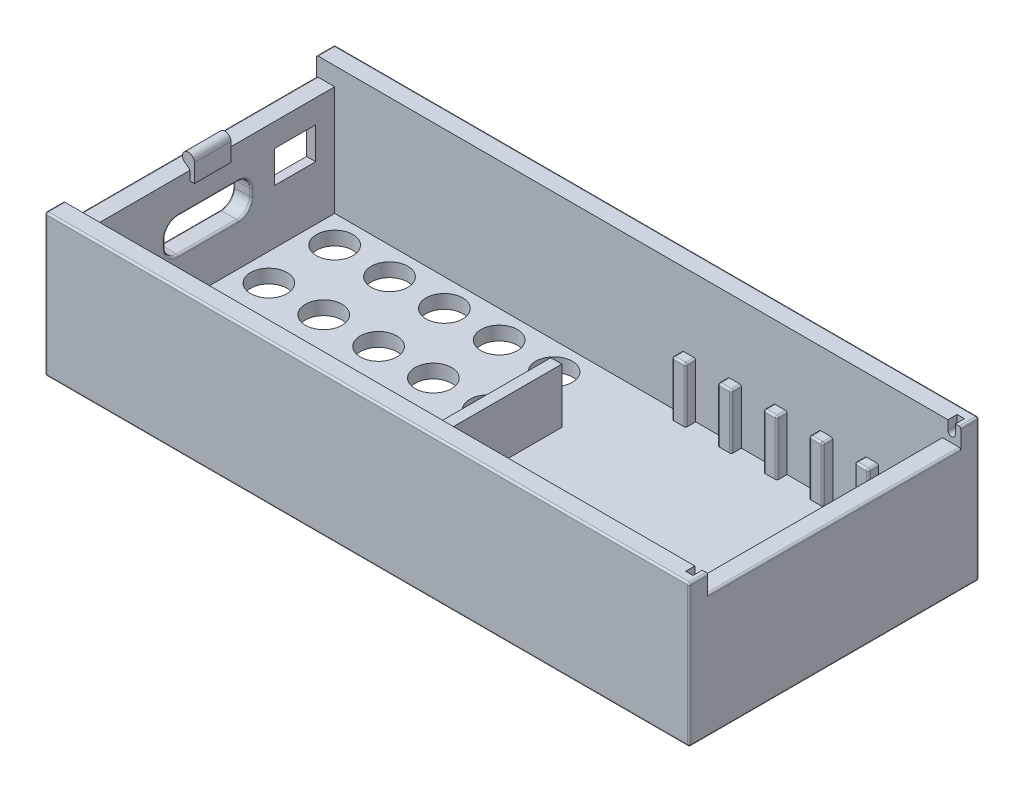
SolidWorks part; units mm, degrees
material "PLA"
ref_plane "前视基准面" through (0, 0, 0) normal (0, 0, 1) x (1, 0, 0)
ref_plane "上视基准面" through (0, 0, 0) normal (0, 1, 0) x (1, 0, 0)
ref_plane "右视基准面" through (0, 0, 0) normal (1, 0, 0) x (0, 0, -1)
sketch "草图1" plane through (0, 0, 0) normal (0, 0, 1) x (1, 0, 0)
  line L0 (0, 0) -> (70.5, 0)
  line L1 (70.5, 0) -> (70.5, 13.5)
  line L2 (70.5, 13.5) -> (68.5, 13.5)
  line L3 (68.5, 13.5) -> (68.5, 1.5)
  line L4 (68.5, 1.5) -> (2, 1.5)
  line L5 (2, 1.5) -> (2, 13.5)
  line L6 (2, 13.5) -> (0, 13.5)
  line L7 (0, 13.5) -> (0, 0)
  dimension "D1" = 66.5
  dimension "D3" = 2
  dimension "D4" = 1.5
  dimension "D6" = 12
extrude "凸台-拉伸1" add sketch "草图1" along normal blind 31.7
sketch "草图3" plane through (0, 1.5, 0) normal (0, 1, 0) x (1, 0, 0)
  line L0 (2, -31.7) -> (68.5, -31.7)
  line L1 (68.5, -31.7) -> (68.5, -29.7)
  line L2 (68.5, -31.7) -> (68.5, 0) construction
  line L3 (68.5, -29.7) -> (2, -29.7)
  line L4 (2, -31.7) -> (2, 0) construction
  line L5 (2, -29.7) -> (2, -31.7)
  dimension "D1" = 2
extrude "凸台-拉伸2" add sketch "草图3" along normal through all
sketch "草图4" plane through (0, 1.5, 0) normal (0, 1, 0) x (1, 0, 0)
  line L0 (2, 0) -> (68.5, 0)
  line L1 (68.5, -29.7) -> (68.5, 0) construction
  line L2 (68.5, -29.7) -> (68.5, 0) construction
  line L3 (68.5, 0) -> (68.5, -2)
  line L4 (68.5, -2) -> (2, -2)
  line L5 (2, -29.7) -> (2, 0) construction
  line L6 (2, -2) -> (2, 0)
  dimension "D1" = 2
extrude "凸台-拉伸3" add sketch "草图4" along normal through all
sketch "草图5" plane through (0, 1.5, 0) normal (0, 1, 0) x (1, 0, 0)
  line L0 (34.1, -6.415) -> (34.1, -25.7073) construction
  line L2 (23.9227, -15.85) -> (46.7103, -15.85) construction
  line L3 (2, -2) -> (68.5, -2) construction
  line L4 (68.5, -29.7) -> (2, -29.7) construction
  line L5 (34.7, -9.85) -> (33.5, -9.85)
  line L6 (33.5, -9.85) -> (33.5, -21.85)
  line L7 (34.7, -9.85) -> (34.7, -21.85)
  line L8 (34.7, -21.85) -> (33.5, -21.85)
  line L9 (2, -29.7) -> (2, -2) construction
  point P14 (34.1, -9.85)
  point P16 (34.7, -15.85)
  point P17 (33.5, -15.85)
  dimension "D1" = 1.2
  dimension "D2" = 32.1
  dimension "D3" = 12
extrude "凸台-拉伸4" add sketch "草图5" along normal blind 6 contours L6 L8 L7 L5
sketch "草图10" plane through (0, 0, 0) normal (-1, 0, 0) x (0, 0, 1)
  line L0 (5.075, 9.1862) -> (7.575, 9.1862) construction
  line L1 (5.075, 8.1862) -> (5.075, 10.1862) construction
  line L2 (7.575, 10.1862) -> (7.575, 8.1862) construction
  line L3 (6.325, 8.1862) -> (6.325, 10.1862) construction
  line L4 (7.575, 8.1862) -> (5.075, 8.1862) construction
  line L5 (5.075, 10.1862) -> (7.575, 10.1862) construction
  line L7 (8.575, 7.4362) -> (4.075, 7.4362)
  line L8 (8.575, 7.4362) -> (8.575, 10.9362)
  line L9 (8.575, 10.9362) -> (4.075, 10.9362)
  line L10 (4.075, 7.4362) -> (4.075, 10.9362)
  line L11 (8.575, 7.4362) -> (4.075, 10.9362) construction
  line L12 (8.575, 10.9362) -> (4.075, 7.4362) construction
  point P12 (6.325, 9.1862)
  dimension "D1" = 3.5
  dimension "D2" = 4.5
extrude "切除-拉伸3" cut sketch "草图10" against normal up to next
sketch "草图11" plane through (0, 0, 0) normal (-1, 0, 0) x (0, 0, 1)
  line L14 (11.13, 8.3362) -> (11.13, 7.5762)
  line L15 (12.58, 6.1262) -> (19.12, 6.1262)
  line L16 (20.57, 7.5762) -> (20.57, 8.3362)
  line L17 (19.12, 9.7862) -> (12.58, 9.7862)
  line L18 (11.13, 8.3362) -> (11.13, 7.5762)
  line L19 (12.58, 6.1262) -> (19.12, 6.1262)
  line L20 (20.57, 7.5762) -> (20.57, 8.3362)
  line L21 (19.12, 9.7862) -> (12.58, 9.7862)
  arc A8 (11.13, 7.5762) -> (12.58, 6.1262) centre (12.58, 7.5762) ccw
  arc A9 (19.12, 6.1262) -> (20.57, 7.5762) centre (19.12, 7.5762) ccw
  arc A10 (20.57, 8.3362) -> (19.12, 9.7862) centre (19.12, 8.3362) ccw
  arc A11 (12.58, 9.7862) -> (11.13, 8.3362) centre (12.58, 8.3362) ccw
  arc A12 (11.13, 7.5762) -> (12.58, 6.1262) centre (12.58, 7.5762) ccw
  arc A13 (19.12, 6.1262) -> (20.57, 7.5762) centre (19.12, 7.5762) ccw
  arc A14 (20.57, 8.3362) -> (19.12, 9.7862) centre (19.12, 8.3362) ccw
  arc A15 (12.58, 9.7862) -> (11.13, 8.3362) centre (12.58, 8.3362) ccw
  dimension "D1" = 0.3
extrude "切除-拉伸4" cut sketch "草图11" against normal up to next
sketch "草图14" plane through (0, 0, 2) normal (0, 0, 1) x (1, 0, 0)
  line L0 (66.4954, 1.5) -> (66.4954, 7.5)
  line L1 (2, 1.5) -> (68.5, 1.5) construction
  line L2 (66.4954, 7.5) -> (64.9954, 7.5)
  line L3 (64.9954, 7.5) -> (64.9954, 1.5)
  line L4 (64.9954, 1.5) -> (66.4954, 1.5)
  line L5 (68.5, 13.5) -> (68.5, 1.5) construction
  line L6 (64.1133, 1.5) -> (64.1133, 7.9181) construction
  line L7 (59.9954, 7.5) -> (59.9954, 1.5)
  line L8 (61.4954, 7.5) -> (59.9954, 7.5)
  line L9 (61.4954, 1.5) -> (61.4954, 7.5)
  line L10 (59.9954, 1.5) -> (61.4954, 1.5)
  line L11 (54.9954, 7.5) -> (54.9954, 1.5)
  line L12 (56.4954, 7.5) -> (54.9954, 7.5)
  line L13 (56.4954, 1.5) -> (56.4954, 7.5)
  line L14 (54.9954, 1.5) -> (56.4954, 1.5)
  line L15 (49.9954, 7.5) -> (49.9954, 1.5)
  line L16 (51.4954, 7.5) -> (49.9954, 7.5)
  line L17 (51.4954, 1.5) -> (51.4954, 7.5)
  line L18 (49.9954, 1.5) -> (51.4954, 1.5)
  line L19 (44.9954, 7.5) -> (44.9954, 1.5)
  line L20 (46.4954, 7.5) -> (44.9954, 7.5)
  line L21 (46.4954, 1.5) -> (46.4954, 7.5)
  line L22 (44.9954, 1.5) -> (46.4954, 1.5)
  line L23 (39.9954, 7.5) -> (39.9954, 1.5)
  line L24 (41.4954, 7.5) -> (39.9954, 7.5)
  line L25 (41.4954, 1.5) -> (41.4954, 7.5)
  line L26 (39.9954, 1.5) -> (41.4954, 1.5)
  line L27 (64.9954, 7.5) -> (59.9954, 7.5) construction
  dimension "D1" = 1.5
  dimension "D2" = 6
  dimension "D3" = 2.0046
  dimension "D4" = 0.8821
  dimension "D6" = 5
  dimension "D5" = 6
extrude "凸台-拉伸7" add sketch "草图14" along normal blind 1.1
fillet "圆角5" radius 0.2 18 edges at (66.4954, 4.5, 3.1) (65.7454, 7.5, 3.1) (64.9954, 4.5, 3.1) (61.4954, 4.5, 3.1) (60.7454, 7.5, 3.1) (59.9954, 4.5, 3.1) (56.4954, 4.5, 3.1) (55.7454, 7.5, 3.1) (54.9954, 4.5, 3.1) (51.4954, 4.5, 3.1) (50.7454, 7.5, 3.1) (49.9954, 4.5, 3.1) (46.4954, 4.5, 3.1) (45.7454, 7.5, 3.1) (44.9954, 4.5, 3.1) (41.4954, 4.5, 3.1) (40.7454, 7.5, 3.1) (39.9954, 4.5, 3.1)
fillet "圆角6" radius 0.2 24 edges at (66.4368, 7.4414, 3.0414) (65.0539, 7.4414, 3.0414) (60.0539, 7.4414, 3.0414) (61.4368, 7.4414, 3.0414) (56.4368, 7.4414, 3.0414) (51.4368, 7.4414, 3.0414) (46.4368, 7.4414, 3.0414) (41.4368, 7.4414, 3.0414) (55.0539, 7.4414, 3.0414) (50.0539, 7.4414, 3.0414) (45.0539, 7.4414, 3.0414) (40.0539, 7.4414, 3.0414) (66.4954, 7.5, 2.45) (64.9954, 7.5, 2.45) (59.9954, 7.5, 2.45) (61.4954, 7.5, 2.45) (56.4954, 7.5, 2.45) (51.4954, 7.5, 2.45) (46.4954, 7.5, 2.45) (41.4954, 7.5, 2.45) (54.9954, 7.5, 2.45) (49.9954, 7.5, 2.45) (44.9954, 7.5, 2.45) (39.9954, 7.5, 2.45)
sketch "草图15" plane through (0, 0, 29.7) normal (0, 0, -1) x (-1, 0, 0)
  line L0 (-68.5, 1.5) -> (-2, 1.5) construction
  line L1 (-66.5, 1.5) -> (-65, 1.5)
  line L2 (-66.5, 1.5) -> (-66.5, 7.5)
  line L3 (-66.5, 7.5) -> (-65, 7.5)
  line L4 (-65, 1.5) -> (-65, 7.5)
  line L5 (-68.5, 13.5) -> (-68.5, 1.5) construction
  line L6 (-61.5, 1.5) -> (-61.5, 7.5)
  line L7 (-61.5, 7.5) -> (-60, 7.5)
  line L8 (-60, 1.5) -> (-60, 7.5)
  line L9 (-61.5, 1.5) -> (-60, 1.5)
  line L10 (-56.5, 1.5) -> (-56.5, 7.5)
  line L11 (-56.5, 7.5) -> (-55, 7.5)
  line L12 (-55, 1.5) -> (-55, 7.5)
  line L13 (-56.5, 1.5) -> (-55, 1.5)
  line L14 (-51.5, 1.5) -> (-51.5, 7.5)
  line L15 (-51.5, 7.5) -> (-50, 7.5)
  line L16 (-50, 1.5) -> (-50, 7.5)
  line L17 (-51.5, 1.5) -> (-50, 1.5)
  line L18 (-46.5, 1.5) -> (-46.5, 7.5)
  line L19 (-46.5, 7.5) -> (-45, 7.5)
  line L20 (-45, 1.5) -> (-45, 7.5)
  line L21 (-46.5, 1.5) -> (-45, 1.5)
  line L22 (-41.5, 1.5) -> (-41.5, 7.5)
  line L23 (-41.5, 7.5) -> (-40, 7.5)
  line L24 (-40, 1.5) -> (-40, 7.5)
  line L25 (-41.5, 1.5) -> (-40, 1.5)
  line L26 (-66.5, 1.5) -> (-61.5, 1.5) construction
  dimension "D1" = 2
  dimension "D2" = 1.5
  dimension "D3" = 6
  dimension "D5" = 5
  dimension "D4" = 6
extrude "凸台-拉伸8" add sketch "草图15" along normal blind 1.1
fillet "圆角7" radius 0.2 30 edges at (40, 7.5, 29.15) (40.75, 7.5, 28.6) (40, 4.5, 28.6) (41.5, 4.5, 28.6) (41.5, 7.5, 29.15) (45, 4.5, 28.6) (46.5, 4.5, 28.6) (45, 7.5, 29.15) (45.75, 7.5, 28.6) (46.5, 7.5, 29.15) (50, 7.5, 29.15) (50, 4.5, 28.6) (50.75, 7.5, 28.6) (51.5, 4.5, 28.6) (51.5, 7.5, 29.15) (55, 7.5, 29.15) (55.75, 7.5, 28.6) (55, 4.5, 28.6) (56.5, 4.5, 28.6) (56.5, 7.5, 29.15) (61.5, 7.5, 29.15) (60, 7.5, 29.15) (60.75, 7.5, 28.6) (60, 4.5, 28.6) (61.5, 4.5, 28.6) (66.5, 4.5, 28.6) (65, 4.5, 28.6) (65, 7.5, 29.15) (65.75, 7.5, 28.6) (66.5, 7.5, 29.15)
sketch "草图16" plane through (0, 0, 0) normal (-1, 0, 0) x (0, 0, 1)
  line L0 (0, 13.5) -> (0, 15.5)
  line L1 (0, 15.5) -> (2, 15.5)
  line L2 (2, 15.5) -> (2, 13.5)
  line L3 (31.7, 13.5) -> (0, 13.5) construction
  line L4 (2, 13.5) -> (0, 13.5)
  line L5 (15.85, 0) -> (15.85, 20.1555) construction
  line L6 (31.7, 0) -> (0, 0) construction
  line L7 (29.7, 13.5) -> (31.7, 13.5)
  line L8 (29.7, 15.5) -> (29.7, 13.5)
  line L9 (31.7, 15.5) -> (29.7, 15.5)
  line L10 (31.7, 13.5) -> (31.7, 15.5)
  dimension "D1" = 2
  dimension "D2" = 2
extrude "凸台-拉伸9" add sketch "草图16" against normal through all
fillet "圆角8" radius 0.2 8 edges at (0, 6.5509, 20.1453) (0, 6.1262, 15.85) (0, 6.5509, 11.5547) (0, 7.9562, 11.13) (0, 9.3615, 11.5547) (0, 9.7862, 15.85) (0, 9.3615, 20.1453) (0, 7.9562, 20.57)
fillet "圆角9" radius 0.2 4 edges at (70.5, 13.5, 15.85) (0, 13.5, 15.85) (35.25, 15.5, 0) (35.25, 15.5, 31.7)
fillet "圆角10" radius 0.2 16 edges at (70.5, 15.5, 1.1) (70.5, 15.4414, 0.0586) (70.5, 15.5, 30.6) (70.5, 15.4414, 31.6414) (0, 15.5, 30.6) (0, 15.4414, 31.6414) (0, 15.5, 1.1) (0, 15.4414, 0.0586) (35.25, 0, 0) (70.5, 0, 15.85) (70.5, 7.65, 0) (70.5, 7.65, 31.7) (35.25, 0, 31.7) (0, 7.65, 31.7) (0, 0, 15.85) (0, 7.65, 0)
fillet "圆角11" radius 0.2 8 edges at (2, 6.5509, 20.1453) (2, 7.9562, 20.57) (2, 9.3615, 20.1453) (2, 9.7862, 15.85) (2, 9.3615, 11.5547) (2, 7.9562, 11.13) (2, 6.5509, 11.5547) (2, 6.1262, 15.85)
sketch "草图17" plane through (0, 0, 0) normal (-1, 0, 0) x (0, 0, 1)
  line L8 (9.575, 6.4362) -> (9.575, 11.9362)
  line L9 (3.075, 6.4362) -> (9.575, 6.4362)
  line L10 (3.075, 11.9362) -> (3.075, 6.4362)
  line L11 (9.575, 11.9362) -> (3.075, 11.9362)
  line L12 (9.575, 6.4362) -> (9.575, 11.9362)
  line L13 (3.075, 6.4362) -> (9.575, 6.4362)
  line L14 (3.075, 11.9362) -> (3.075, 6.4362)
  line L15 (9.575, 11.9362) -> (3.075, 11.9362)
  dimension "D1" = 1
extrude "切除-拉伸5" cut sketch "草图17" against normal blind 1
chamfer "倒角1" distance 0.5 angle 45 4 edges at (0, 9.1862, 9.575) (0, 11.9362, 6.325) (0, 9.1862, 3.075) (0, 6.4362, 6.325)
sketch "草图18" plane through (0, 1.5, 0) normal (0, 1, 0) x (1, 0, 0)
  line L0 (5, -5) -> (11, -5) construction
  line L1 (5, -5) -> (5, -12.2) construction
  line L2 (5, -5) -> (11, -5) construction
  circle A0 centre (5, -5) radius 2
  circle A1 centre (11, -5) radius 2
  circle A2 centre (17, -5) radius 2
  circle A3 centre (23, -5) radius 2
  circle A4 centre (29, -5) radius 2
  circle A5 centre (5, -12.2) radius 2
  circle A6 centre (5, -19.4) radius 2
  circle A7 centre (5, -26.6) radius 2
  circle A8 centre (11, -5) radius 2
  circle A9 centre (11, -12.2) radius 2
  circle A10 centre (11, -19.4) radius 2
  circle A11 centre (11, -26.6) radius 2
  circle A12 centre (17, -5) radius 2
  circle A13 centre (17, -12.2) radius 2
  circle A14 centre (17, -19.4) radius 2
  circle A15 centre (17, -26.6) radius 2
  circle A16 centre (23, -5) radius 2
  circle A17 centre (23, -12.2) radius 2
  circle A18 centre (23, -19.4) radius 2
  circle A19 centre (23, -26.6) radius 2
  circle A20 centre (29, -5) radius 2
  circle A21 centre (29, -12.2) radius 2
  circle A22 centre (29, -19.4) radius 2
  circle A23 centre (29, -26.6) radius 2
  dimension "D1" = 5
  dimension "D2" = 5
  dimension "D3" = 4
  dimension "D5" = 6
  dimension "D7" = 7.2
  dimension "D9" = 6
  dimension "D4" = 5
  dimension "D6" = 4
  dimension "D8" = 5
extrude "切除-拉伸6" cut sketch "草图18" against normal through all contours A11 | A10 | A7 | A6 | A14 | A18 | A22 | A15 | A19 | A23 | A21 | A17 | A13 | A9 | A5 | A0 | A1 | A2 | A3 | A4 region at (5, 1.5, 5) region at (11, 1.5, 5) region at (17, 1.5, 5) region at (23, 1.5, 5) region at (29, 1.5, 5) region at (5, 1.5, 12.2) region at (5, 1.5, 19.4) region at (5, 1.5, 26.6) region at (11, 1.5, 12.2) region at (11, 1.5, 19.4) region at (11, 1.5, 26.6) region at (17, 1.5, 12.2) region at (17, 1.5, 19.4) region at (17, 1.5, 26.6) region at (23, 1.5, 12.2) region at (23, 1.5, 19.4) region at (23, 1.5, 26.6) region at (29, 1.5, 12.2) region at (29, 1.5, 19.4) region at (29, 1.5, 26.6)
sketch "草图19" plane through (0, 0, 2) normal (0, 0, 1) x (1, 0, 0)
  line L0 (68.5, 13.5) -> (70.5, 13.5) construction
  line L1 (70.5, 13.3) -> (70.5, 15.3) construction
  line L2 (69.5, 13.5) -> (69.5, 15.5) construction
  line L3 (70.3, 15.5) -> (0.2, 15.5) construction
  line L4 (69.9, 14.5) -> (69.9, 15.5)
  line L5 (69.1, 14.5) -> (69.1, 15.5)
  line L6 (69.1, 15.5) -> (69.9, 15.5)
  arc A0 (69.1, 14.5) -> (69.9, 14.5) centre (69.5, 14.5) ccw
  dimension "D1" = 0.8
extrude "切除-拉伸7" cut sketch "草图19" against normal blind 1
sketch "草图20" plane through (0, 0, 29.7) normal (0, 0, -1) x (-1, 0, 0)
  line L0 (-69.9, 14.5) -> (-69.9, 15.5) construction
  line L1 (-69.1, 15.5) -> (-69.1, 14.5) construction
  line L2 (-69.9, 14.5) -> (-69.9, 15.5)
  line L3 (-69.1, 15.5) -> (-69.1, 14.5)
  line L4 (-69.9, 15.5) -> (-69.1, 15.5)
  line L32 (-0.2, 15.5) -> (-70.3, 15.5)
  line L33 (-70.5, 15.3) -> (-70.5, 13.3)
  line L34 (-70.3, 13.5) -> (-68.5, 13.5)
  line L35 (-68.5, 13.5) -> (-68.5, 1.5)
  line L36 (-68.5, 1.5) -> (-66.5, 1.5)
  line L37 (-66.5, 1.5) -> (-66.5, 7.3)
  line L38 (-66.3, 7.5) -> (-65.2, 7.5)
  line L39 (-65, 7.3) -> (-65, 1.5)
  line L40 (-65, 1.5) -> (-61.5, 1.5)
  line L41 (-61.5, 1.5) -> (-61.5, 7.3)
  line L42 (-61.3, 7.5) -> (-60.2, 7.5)
  line L43 (-60, 7.3) -> (-60, 1.5)
  line L44 (-60, 1.5) -> (-56.5, 1.5)
  line L45 (-56.5, 1.5) -> (-56.5, 7.3)
  line L46 (-56.3, 7.5) -> (-55.2, 7.5)
  line L47 (-55, 7.3) -> (-55, 1.5)
  line L48 (-55, 1.5) -> (-51.5, 1.5)
  line L49 (-51.5, 1.5) -> (-51.5, 7.3)
  line L50 (-51.3, 7.5) -> (-50.2, 7.5)
  line L51 (-50, 7.3) -> (-50, 1.5)
  line L52 (-50, 1.5) -> (-46.5, 1.5)
  line L53 (-46.5, 1.5) -> (-46.5, 7.3)
  line L54 (-46.3, 7.5) -> (-45.2, 7.5)
  line L55 (-45, 7.3) -> (-45, 1.5)
  line L56 (-45, 1.5) -> (-41.5, 1.5)
  line L57 (-41.5, 1.5) -> (-41.5, 7.3)
  line L58 (-41.3, 7.5) -> (-40.2, 7.5)
  line L59 (-40, 7.3) -> (-40, 1.5)
  line L60 (-40, 1.5) -> (-2, 1.5)
  line L61 (-2, 1.5) -> (-2, 13.5)
  line L62 (-2, 13.5) -> (-0.2, 13.5)
  line L63 (0, 13.3) -> (0, 15.3)
  line L64 (-0.2, 15.5) -> (-70.3, 15.5)
  line L65 (-70.5, 15.3) -> (-70.5, 13.3)
  line L66 (-70.3, 13.5) -> (-68.5, 13.5)
  line L67 (-68.5, 13.5) -> (-68.5, 1.5)
  line L68 (-68.5, 1.5) -> (-66.5, 1.5)
  line L69 (-66.5, 1.5) -> (-66.5, 7.3)
  line L70 (-66.3, 7.5) -> (-65.2, 7.5)
  line L71 (-65, 7.3) -> (-65, 1.5)
  line L72 (-65, 1.5) -> (-61.5, 1.5)
  line L73 (-61.5, 1.5) -> (-61.5, 7.3)
  line L74 (-61.3, 7.5) -> (-60.2, 7.5)
  line L75 (-60, 7.3) -> (-60, 1.5)
  line L76 (-60, 1.5) -> (-56.5, 1.5)
  line L77 (-56.5, 1.5) -> (-56.5, 7.3)
  line L78 (-56.3, 7.5) -> (-55.2, 7.5)
  line L79 (-55, 7.3) -> (-55, 1.5)
  line L80 (-55, 1.5) -> (-51.5, 1.5)
  line L81 (-51.5, 1.5) -> (-51.5, 7.3)
  line L82 (-51.3, 7.5) -> (-50.2, 7.5)
  line L83 (-50, 7.3) -> (-50, 1.5)
  line L84 (-50, 1.5) -> (-46.5, 1.5)
  line L85 (-46.5, 1.5) -> (-46.5, 7.3)
  line L86 (-46.3, 7.5) -> (-45.2, 7.5)
  line L87 (-45, 7.3) -> (-45, 1.5)
  line L88 (-45, 1.5) -> (-41.5, 1.5)
  line L89 (-41.5, 1.5) -> (-41.5, 7.3)
  line L90 (-41.3, 7.5) -> (-40.2, 7.5)
  line L91 (-40, 7.3) -> (-40, 1.5)
  line L92 (-40, 1.5) -> (-2, 1.5)
  line L93 (-2, 1.5) -> (-2, 13.5)
  line L94 (-2, 13.5) -> (-0.2, 13.5)
  line L95 (0, 13.3) -> (0, 15.3)
  arc A0 (-69.9, 14.5) -> (-69.1, 14.5) centre (-69.5, 14.5) ccw construction
  arc A1 (-69.9, 14.5) -> (-69.1, 14.5) centre (-69.5, 14.5) ccw
  arc A16 (-70.3, 15.5) -> (-70.5, 15.3) centre (-70.3, 15.3) ccw
  arc A17 (-70.3, 13.5) -> (-70.5, 13.3) centre (-70.3, 13.3) ccw
  arc A18 (-66.3, 7.5) -> (-66.5, 7.3) centre (-66.3, 7.3) ccw
  arc A19 (-65, 7.3) -> (-65.2, 7.5) centre (-65.2, 7.3) ccw
  arc A20 (-61.3, 7.5) -> (-61.5, 7.3) centre (-61.3, 7.3) ccw
  arc A21 (-60, 7.3) -> (-60.2, 7.5) centre (-60.2, 7.3) ccw
  arc A22 (-56.3, 7.5) -> (-56.5, 7.3) centre (-56.3, 7.3) ccw
  arc A23 (-55, 7.3) -> (-55.2, 7.5) centre (-55.2, 7.3) ccw
  arc A24 (-51.3, 7.5) -> (-51.5, 7.3) centre (-51.3, 7.3) ccw
  arc A25 (-50, 7.3) -> (-50.2, 7.5) centre (-50.2, 7.3) ccw
  arc A26 (-46.3, 7.5) -> (-46.5, 7.3) centre (-46.3, 7.3) ccw
  arc A27 (-45, 7.3) -> (-45.2, 7.5) centre (-45.2, 7.3) ccw
  arc A28 (-41.3, 7.5) -> (-41.5, 7.3) centre (-41.3, 7.3) ccw
  arc A29 (-40, 7.3) -> (-40.2, 7.5) centre (-40.2, 7.3) ccw
  arc A30 (0, 13.3) -> (-0.2, 13.5) centre (-0.2, 13.3) ccw
  arc A31 (0, 15.3) -> (-0.2, 15.5) centre (-0.2, 15.3) ccw
  arc A32 (-70.3, 15.5) -> (-70.5, 15.3) centre (-70.3, 15.3) ccw
  arc A33 (-70.3, 13.5) -> (-70.5, 13.3) centre (-70.3, 13.3) ccw
  arc A34 (-66.3, 7.5) -> (-66.5, 7.3) centre (-66.3, 7.3) ccw
  arc A35 (-65, 7.3) -> (-65.2, 7.5) centre (-65.2, 7.3) ccw
  arc A36 (-61.3, 7.5) -> (-61.5, 7.3) centre (-61.3, 7.3) ccw
  arc A37 (-60, 7.3) -> (-60.2, 7.5) centre (-60.2, 7.3) ccw
  arc A38 (-56.3, 7.5) -> (-56.5, 7.3) centre (-56.3, 7.3) ccw
  arc A39 (-55, 7.3) -> (-55.2, 7.5) centre (-55.2, 7.3) ccw
  arc A40 (-51.3, 7.5) -> (-51.5, 7.3) centre (-51.3, 7.3) ccw
  arc A41 (-50, 7.3) -> (-50.2, 7.5) centre (-50.2, 7.3) ccw
  arc A42 (-46.3, 7.5) -> (-46.5, 7.3) centre (-46.3, 7.3) ccw
  arc A43 (-45, 7.3) -> (-45.2, 7.5) centre (-45.2, 7.3) ccw
  arc A44 (-41.3, 7.5) -> (-41.5, 7.3) centre (-41.3, 7.3) ccw
  arc A45 (-40, 7.3) -> (-40.2, 7.5) centre (-40.2, 7.3) ccw
  arc A46 (0, 13.3) -> (-0.2, 13.5) centre (-0.2, 13.3) ccw
  arc A47 (0, 15.3) -> (-0.2, 15.5) centre (-0.2, 15.3) ccw
  dimension "D1" = 0
extrude "切除-拉伸8" cut sketch "草图20" against normal blind 1 contours L4 L3 A1 L2
ref_plane "基准面1" through (0, 0, 15.85) normal (0, 0, -1) x (-1, 0, 0)
sketch "草图22" plane through (0, 0, 15.85) normal (0, 0, -1) x (-1, 0, 0)
  line L0 (-2, 13.5) -> (-2, 1.5) construction
  line L1 (-2, 13.5) -> (-0.2, 13.5) construction
  line L2 (-2, 13.5) -> (-2, 1.5) construction
  line L3 (-2, 13.5) -> (-0.2, 13.5) construction
  line L7 (-2, 12.5) -> (-2.5, 12.5)
  line L8 (-2.5, 12.5) -> (-2.5, 14.5)
  line L9 (-2, 13.5) -> (-2, 13.8675)
  line L10 (-2, 12.5) -> (-2, 13.5)
  arc A1 (-2, 13.8675) -> (-2.5, 14.5) centre (-1.85, 14.5) ccw
  dimension "D1" = 1.3
  dimension "D2" = 2
  dimension "D3" = 1
  dimension "D4" = 0.5
extrude "凸台-拉伸10" add sketch "草图22" along normal mid plane 4
fillet "圆角13" radius 1 1 edges at (2, 13.8675, 15.85)
